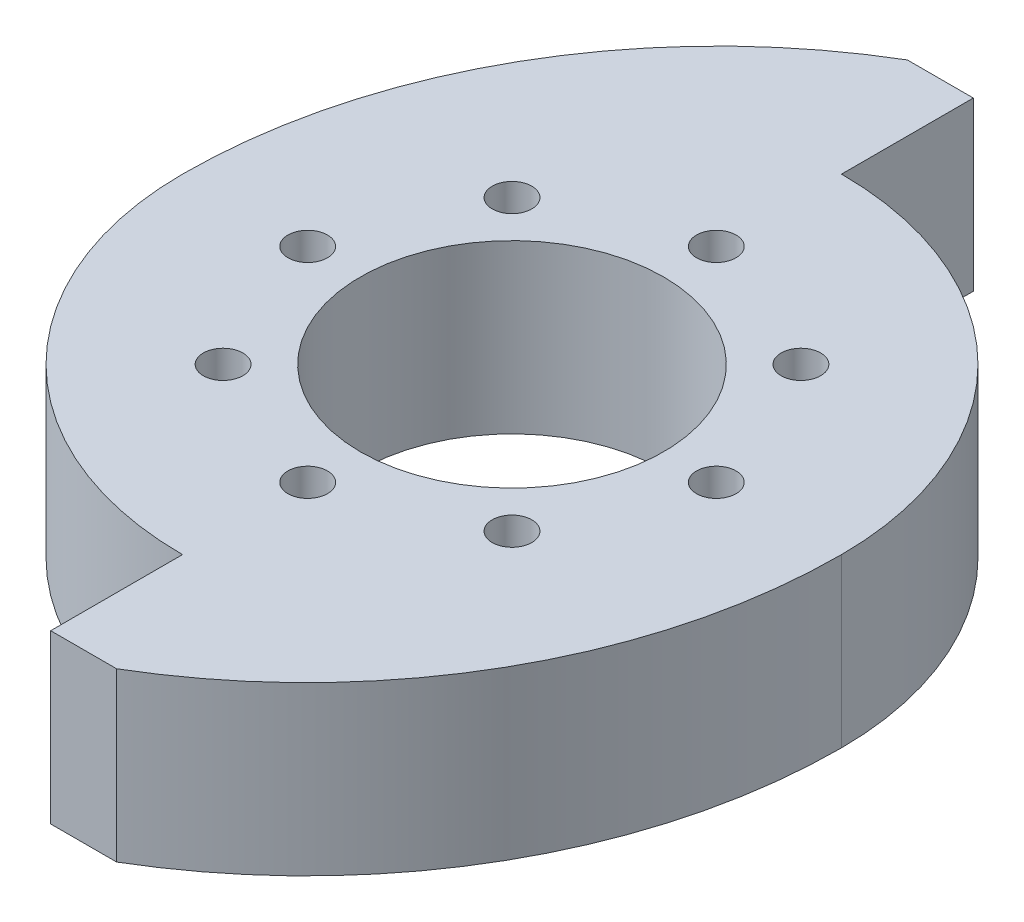
SolidWorks part; units mm, degrees
material "Plain Carbon Steel"
ref_plane "Front Plane" through (0, 0, 0) normal (0, 0, 1) x (1, 0, 0)
ref_plane "Top Plane" through (0, 0, 0) normal (0, 1, 0) x (1, 0, 0)
ref_plane "Right Plane" through (0, 0, 0) normal (1, 0, 0) x (0, 0, -1)
ref_axis "X" through (-88.99, 0, 0) along (1, 0, 0)
ref_axis "Y" through (0, 55, 0) along (0, -1, 0)
ref_axis "Z" through (0, 0, -88.99) along (0, 0, 1)
sketch "Sketch1" plane through (0, 0, 0) normal (0, 1, 0) x (1, 0, 0)
  line L0 (0, 25) -> (0, 35)
  line L1 (0, 35) -> (-5, 35)
  line L2 (0, -25) -> (0, -35)
  line L3 (0, -35) -> (5, -35)
  line L4 (0, 11.5) -> (0, 25) construction
  circle A0 centre (0, 0) radius 25
  arc A1 (-5, 35) -> (-25, 0) centre (15.625, 0) ccw
  arc A2 (5, -35) -> (25, 0) centre (-15.625, 0) ccw
  circle A3 centre (0, 0) radius 11.5
  circle A4 centre (0, 15.5) radius 1.5
  circle A5 centre (10.9602, 10.9602) radius 1.5
  circle A6 centre (15.5, 0) radius 1.5
  circle A7 centre (10.9602, -10.9602) radius 1.5
  circle A8 centre (0, -15.5) radius 1.5
  circle A9 centre (-10.9602, -10.9602) radius 1.5
  circle A10 centre (-15.5, 0) radius 1.5
  circle A11 centre (-10.9602, 10.9602) radius 1.5
  point P16 (0, 0)
  point P18 (0.2402, 16.0665)
  point P19 (0, 15.1721)
  point P35 (0, 0)
  dimension "D1" = 50
  dimension "D4" = 2
  dimension "D5" = 23
  dimension "D6" = 3
  dimension "D2" = 10
  dimension "D3" = 5
  dimension "D8" = 4
  dimension "D7" = 8
extrude "Boss-Extrude1" add sketch "Sketch1" along normal mid plane 12.7 contours A0 A3 | L1 A1 A0 L0 | L3 A2 A0 L2 region at (-9.8514, 0, -25.8127) region at (17.1777, 0, -17.1777) region at (9.8514, 0, 25.8127)
